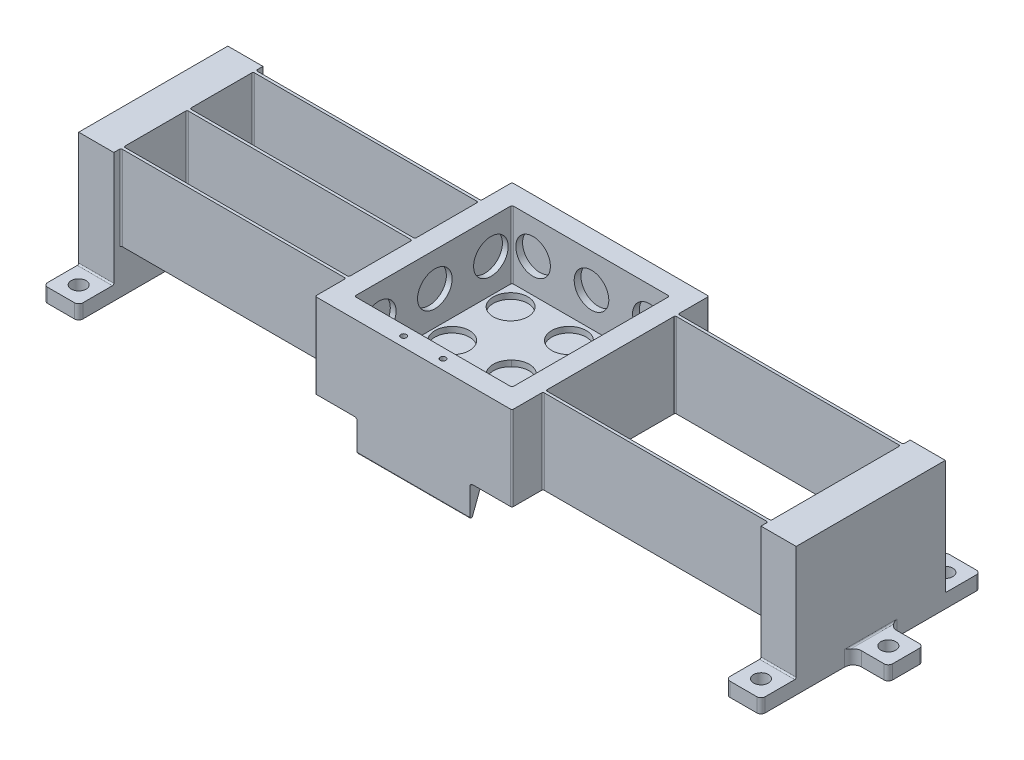
SolidWorks part; units mm, degrees
ref_plane "Front Plane" through (0, 0, 0) normal (0, 0, 1) x (1, 0, 0)
ref_plane "Top Plane" through (0, 0, 0) normal (0, 1, 0) x (1, 0, 0)
ref_plane "Right Plane" through (0, 0, 0) normal (1, 0, 0) x (0, 0, -1)
sketch "Sketch1" plane through (0, 0, 0) normal (0, 1, 0) x (1, 0, 0)
  line L1 (-35, -35) -> (35, -35)
  line L2 (-35, -35) -> (-35, 35)
  line L3 (-35, 35) -> (35, 35)
  line L4 (35, -35) -> (35, 35)
  line L5 (-35, -35) -> (35, 35) construction
  line L6 (-35, 35) -> (35, -35) construction
  point P0 (0, 0)
  dimension "D1" = 70
  dimension "D2" = 70
extrude "Boss-Extrude1" add sketch "Sketch1" along normal blind 30
shell "Shell1" thickness 7 removed face at (0, 30, 0)
sketch "Sketch2" plane through (0, 30, 0) normal (0, 1, 0) x (1, 0, 0)
  line L0 (-35, 35) -> (-35, -35) construction
  line L1 (-28, -28) -> (28, -28) construction
  line L2 (-28, -28) -> (-28, 28) construction
  line L3 (-28, 28) -> (28, 28) construction
  line L4 (28, -28) -> (28, 28) construction
  line L5 (-28, -28) -> (28, 28) construction
  line L6 (-28, 28) -> (28, -28) construction
  line L7 (35, 35) -> (-35, 35) construction
  point P0 (0, 0)
  dimension "D1" = 7
  dimension "D2" = 7
sketch "Sketch3" plane through (35, 0, 0) normal (1, 0, 0) x (0, 0, -1)
  line L0 (-35, 30) -> (35, 30) construction
  line L1 (-24, 30) -> (-23, 30)
  line L2 (-24, 30) -> (-24, 0)
  line L3 (-24, 0) -> (-23, 0)
  line L4 (-23, 30) -> (-23, 0)
  line L5 (-35, 0) -> (35, 0) construction
  line L6 (-28, 30) -> (28, 30) construction
  line L7 (-0.5, 30) -> (0.5, 30)
  line L8 (-0.5, 30) -> (-0.5, 0)
  line L9 (-0.5, 0) -> (0.5, 0)
  line L10 (0.5, 30) -> (0.5, 0)
  line L11 (28, 30) -> (-28, 30) construction
  line L12 (24, 30) -> (23, 30)
  line L13 (24, 30) -> (24, 0)
  line L14 (24, 0) -> (23, 0)
  line L15 (23, 30) -> (23, 0)
  line L16 (-23.5, 30) -> (-23.5, 0) construction
  line L17 (0, 30) -> (0, 0) construction
  line L18 (23.5, 0) -> (23.5, 30) construction
  dimension "D1" = 23
  dimension "D2" = 23
  dimension "D3" = 1
extrude "Boss-Extrude2" add sketch "Sketch3" along normal blind 80
sketch "Sketch5" plane through (115, 0, 0) normal (1, 0, 0) x (0, 0, -1)
  line L0 (-24, 30) -> (-24, 0) construction
  line L1 (-26.5, 30) -> (26.5, 30)
  line L2 (-26.5, 30) -> (-26.5, 0)
  line L3 (-26.5, 0) -> (26.5, 0)
  line L4 (26.5, 30) -> (26.5, 0)
  line L5 (28, 30) -> (-28, 30) construction
  line L6 (24, 0) -> (35, 0) construction
  line L7 (24, 0) -> (24, 30) construction
  dimension "D1" = 2.5
  dimension "D2" = 2.5
extrude "Boss-Extrude3" add sketch "Sketch5" along normal blind 12.5
sketch "Sketch6" plane through (0, 0, 0) normal (0, -1, 0) x (1, 0, 0)
  line L1 (115, 26.5) -> (127.5, 26.5)
  line L2 (115, 26.5) -> (115, -26.5)
  line L3 (115, -26.5) -> (127.5, -26.5)
  line L4 (127.5, 26.5) -> (127.5, -26.5)
extrude "Boss-Extrude4" add sketch "Sketch6" along normal blind 15.75
sketch "Sketch8" plane through (0, -15.75, 0) normal (0, -1, 0) x (1, 0, 0)
  line L1 (127.5, -26.5) -> (115, -26.5)
  line L2 (127.5, -26.5) -> (127.5, -39)
  line L3 (127.5, -39) -> (115, -39)
  line L4 (115, -26.5) -> (115, -39)
  line L5 (127.5, 26.5) -> (115, 26.5)
  line L6 (127.5, 26.5) -> (127.5, 39)
  line L7 (127.5, 39) -> (115, 39)
  line L8 (115, 26.5) -> (115, 39)
  line L13 (127.5, -26.5) -> (127.5, 26.5) construction
  line L14 (140, -6.25) -> (127.5, -6.25)
  line L15 (140, -6.25) -> (140, 6.25)
  line L16 (140, 6.25) -> (127.5, 6.25)
  line L17 (127.5, -6.25) -> (127.5, 6.25)
  line L18 (140, -6.25) -> (127.5, 6.25) construction
  line L19 (140, 6.25) -> (127.5, -6.25) construction
  line L20 (115, 0) -> (140, 0) construction
  line L21 (115, 0.5) -> (115, -0.5) construction
  point P13 (133.75, 0)
  point P19 (127.5, 0)
  point P20 (127.5, 0)
extrude "Boss-Extrude5" add sketch "Sketch8" against normal blind 5
hole_wizard "Ø5.0mm Dowel Hole1" positions "Sketch9" profile "Sketch10" hole size "Ø5.0" standard "ANSI Metric"
sketch "Sketch9" plane through (0, -10.75, 0) normal (0, 1, 0) x (1, 0, 0)
  line L0 (121.25, 39) -> (121.25, 32.75) construction
  line L1 (115, 39) -> (127.5, 39) construction
  line L2 (121.25, 32.75) -> (127.5, 32.75) construction
  line L3 (127.5, 39) -> (127.5, 26.5) construction
  line L5 (127.5, 0) -> (133.75, 0) construction
  line L6 (127.5, -6.25) -> (127.5, 6.25) construction
  line L7 (133.75, 0) -> (133.75, 6.25) construction
  line L8 (127.5, 6.25) -> (140, 6.25) construction
  line L10 (121.25, -26.5) -> (121.25, -32.75) construction
  line L11 (115, -26.5) -> (127.5, -26.5) construction
  line L12 (121.25, -32.75) -> (127.5, -32.75) construction
  line L13 (127.5, -26.5) -> (127.5, -39) construction
  point P0 (121.25, 32.75)
  point P2 (133.75, 0)
  point P4 (121.25, -32.75)
sketch "Sketch10" plane through (121.25, -10.75, -32.75) normal (1, 0, 0) x (0, 0, 1)
  line L0 (0, 0) -> (0, 18.1023)
  line L1 (0, 18.1023) -> (2.65, 16.51)
  line L2 (2.65, 16.51) -> (2.65, 0)
  line L5 (2.65, 0) -> (0, 0)
  line L10 (0, 18.1023) -> (-2.65, 16.51) construction
  line L11 (0, -6.35) -> (0, 107.95) construction
  dimension "Hole Dia." = 5.3
  dimension "Hole Depth" = 16.51
  dimension "Drill Angle" = 118
mirror "Mirror1" about plane through (0, 0, 0) normal (1, 0, 0) of "Boss-Extrude2", "Boss-Extrude3", "Boss-Extrude5", "Boss-Extrude4", "Ø5.0mm Dowel Hole1"
fillet "Fillet2" radius 1.5 12 edges at (140, -13.25, 6.25) (140, -13.25, -6.25) (127.5, -13.25, -39) (115, -13.25, -39) (127.5, -13.25, 39) (115, -13.25, 39) (-115, -13.25, -39) (-127.5, -13.25, -39) (-140, -13.25, -6.25) (-140, -13.25, 6.25) (-115, -13.25, 39) (-127.5, -13.25, 39)
sketch "Sketch11" plane through (0, 6, 0) normal (0, 1, 0) x (1, 0, 0)
  line L26 (-28, -28) -> (-28, 28) construction
  line L32 (-28, -28) -> (28, -28) construction
  circle A0 centre (-21, -21) radius 6.15
  dimension "D1" = 12.3
  dimension "D2" = 0.85
  dimension "D3" = 0.85
extrude "Cut-Extrude1" cut sketch "Sketch11" against normal blind 2.05
pattern_linear "LPattern1" count 3 spacing 20.75 along (1, 0, 0) count 3 spacing 20.75 along (0, 0, -1) of "Cut-Extrude1"
sketch "Sketch14" plane through (0, 6, 0) normal (0, 1, 0) x (1, 0, 0)
  line L0 (-28, 0) -> (0, 0) construction
  line L1 (-28, 28) -> (-28, -28) construction
  line L2 (0, 0) -> (0, -28) construction
  line L3 (-28, -28) -> (28, -28) construction
  circle A0 centre (0, 0) radius 6.15
  dimension "D1" = 12.3
extrude "Cut-Extrude4" cut sketch "Sketch14" against normal blind 2.05
sketch "Sketch12" plane through (-28, 0, 0) normal (1, 0, 0) x (0, 0, -1)
  line L5 (-28, 18) -> (-19.35, 18) construction
  line L6 (-28, 30) -> (-28, 6) construction
  circle A0 centre (-19.35, 18) radius 6.15
  dimension "D1" = 12.3
  dimension "D2" = 2.5
extrude "Cut-Extrude2" cut sketch "Sketch12" against normal blind 2.05
pattern_linear "LPattern2" count 3 spacing 19.925 along (0, 0, -1) of "Cut-Extrude2"
sketch "Sketch13" plane through (0, 0, -28) normal (0, 0, -1) x (-1, 0, 0)
  line L6 (-28, 30) -> (-28, 6) construction
  line L7 (-21, 18) -> (-28, 18) construction
  circle A0 centre (-21, 18) radius 6.15
  dimension "D1" = 12.3
  dimension "D3" = 0.85
extrude "Cut-Extrude3" cut sketch "Sketch13" along normal blind 2.4
pattern_linear "LPattern3" count 3 spacing 20.75 along (-1, 0, 0) of "Cut-Extrude3"
mirror "Mirror2" about plane through (0, 0, 0) normal (1, 0, 0) of "LPattern2", "Cut-Extrude2"
sketch "Sketch24" plane through (0, 30, 0) normal (0, 1, 0) x (1, 0, 0)
  line L1 (35, 0.5) -> (115, 0.5)
  line L2 (35, 0.5) -> (35, -0.5)
  line L3 (35, -0.5) -> (115, -0.5)
  line L4 (115, 0.5) -> (115, -0.5)
extrude "Cut-Extrude6" cut sketch "Sketch24" against normal through all both and the other way through all
fillet "Fillet4" radius 0.5 4 edges at (-35, 15, 35) (35, 15, 35) (-35, 15, -35) (35, 15, -35)
sketch "Sketch19" plane through (0, 0, 0) normal (1, 0, 0) x (0, 0, -1)
  line L0 (-30, 0) -> (-35, -13.25)
  line L1 (-35, -13.25) -> (-35, 0)
  line L2 (-35, 0) -> (-30, 0)
  line L3 (0, 0) -> (-30, 0) construction
  line L4 (37.5, -15.75) -> (-37.5, -15.75) construction
  dimension "D1" = 5
  dimension "D2" = 30
  dimension "D3" = 2.5
extrude "Boss-Extrude8" add sketch "Sketch19" along normal mid plane 40
sketch "Sketch20" plane through (0, 0, 0) normal (1, 0, 0) x (0, 0, -1)
  line L0 (-35, 20) -> (-42.5, 20)
  line L1 (-42.5, 20) -> (-42.5, 30)
  line L2 (-26.5, 30) -> (-42.5, 30) construction
  line L5 (-42.5, 30) -> (-40, 30)
  line L6 (-40, 30) -> (-40, 22.5)
  line L7 (-40, 22.5) -> (-35, 22.5)
  line L8 (-35, 22.5) -> (-35, 20)
  line L9 (-35, 30) -> (-35, 0) construction
  line L10 (-35, 0) -> (-35, 30) construction
  dimension "D1" = 5
  dimension "D2" = 10
  dimension "D3" = 2.5
  dimension "D4" = 2.5
extrude "Place For Sensor" [suppressed] add sketch "Sketch20" along normal mid plane 10
fillet "Place For Sensor Fillet5" [suppressed] radius 0.5
fillet "Place For Sensor Fillet6" [suppressed] radius 1.5
hole_wizard "Place For Sensor Ø3.0mm Dowel Hole2" [suppressed] positions "Sketch21" profile "Sketch22" hole size "Ø3.0" standard "ANSI Metric"
sketch "Sketch21" [suppressed] plane through (0, 0, 32.5) normal (0, 0, 1) x (1, 0, 0)
  line L0 (-2.5, 27.5) -> (2.5, 27.5) construction
  line L2 (-18, 30) -> (18, 30) construction
  line L3 (-5, 28.5) -> (-5, 20.5) construction
  line L4 (5, 28.5) -> (5, 20.5) construction
  point P0 (-2.5, 27.5)
  point P2 (2.5, 27.5)
  dimension "D1" = 2.5
  dimension "D2" = 2.5
  dimension "D3" = 2.5
sketch "Sketch22" plane through (-2.5, 27.5, 32.5) normal (1, 0, 0) x (0, -1, 0)
  line L0 (0, 0) -> (0, 2.5)
  line L1 (0, 2.5) -> (1.65, 2.5)
  line L2 (1.65, 2.5) -> (1.65, 0)
  line L5 (1.65, 0) -> (0, 0)
  line L11 (0, -6.35) -> (0, 107.95) construction
  dimension "Thru Hole Dia." = 3.3
  dimension "Thru Hole Depth" = 2.5
sketch "Sketch23" plane through (0, 30, 0) normal (0, 1, 0) x (1, 0, 0)
  line L1 (-28, -28) -> (28, -28) construction
  circle A0 centre (-7, -31.5) radius 1
  circle A1 centre (7, -31.5) radius 1
  dimension "D4" = 2
  dimension "D1" = 3.5
  dimension "D2" = 14
  dimension "D3" = 7
extrude "Cut-Extrude5" cut sketch "Sketch23" against normal blind 6
fillet "Fillet3" radius 0.5 4 edges at (28, 18, -28) (-28, 18, -28) (28, 18, 28) (-28, 18, 28)
fillet "Fillet1" radius 0.5 26 edges at (115, 15, 23) (115, 15, 24) (115, 15, -23) (115, 15, -24) (35, 15, 24) (35, 15, 23) (35, 15, -24) (35, 15, -23) (-115, 15, 24) (-115, 15, 23) (-115, 15, 0.5) (-115, 15, -0.5) (-115, 15, -24) (-115, 15, -23) (-35, 15, 24) (-35, 15, 23) (-35, 15, 0.5) (-35, 15, -0.5) (-35, 15, -23) (-35, 15, -24) (-121.25, -10.75, -26.5) (-127.5, -10.75, 0) (-121.25, -10.75, 26.5) (121.25, -10.75, 26.5) (121.25, -10.75, -26.5) (127.5, -10.75, 0)
fillet "Fillet5" radius 0.5 1 edges at (0, -13.25, 35)
fillet "Fillet6" radius 1 3 edges at (-20, 0, 32.5) (20, 0, 32.5) (0, 0, 30)
fillet "Fillet8" radius 3 4 edges at (127.5, -13, 6.25) (127.5, -13, -6.25) (-127.5, -13, -6.25) (-127.5, -13, 6.25)
